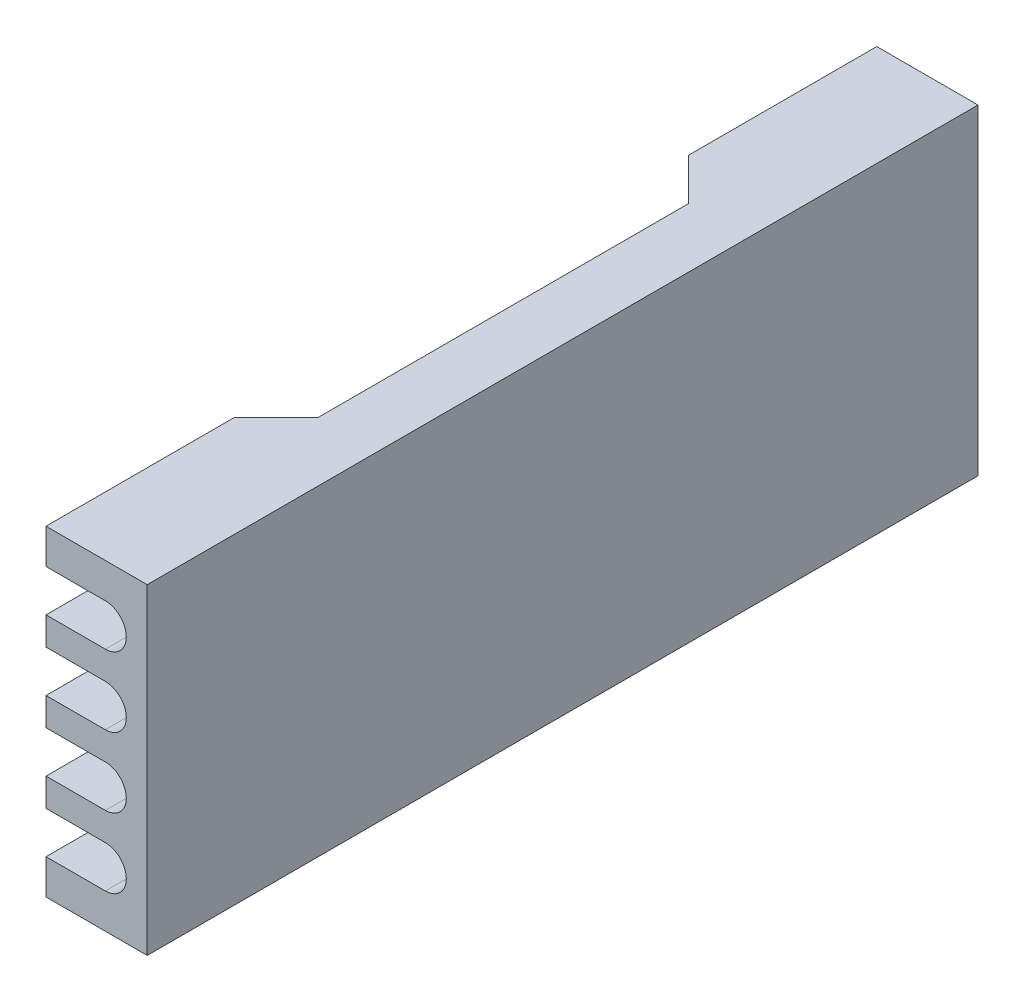
SolidWorks part; units mm, degrees
ref_plane "Front Plane" through (0, 0, 0) normal (0, 0, 1) x (1, 0, 0)
ref_plane "Top Plane" through (0, 0, 0) normal (0, 1, 0) x (1, 0, 0)
ref_plane "Right Plane" through (0, 0, 0) normal (1, 0, 0) x (0, 0, -1)
sketch "Sketch1" plane through (0, 0, 0) normal (1, 0, 0) x (0, 0, -1)
  line L1 (13.335, -5.334) -> (-13.335, -5.334)
  line L2 (13.335, -5.334) -> (13.335, 5.334)
  line L3 (13.335, 5.334) -> (-13.335, 5.334)
  line L4 (-13.335, -5.334) -> (-13.335, 5.334)
  line L5 (13.335, -5.334) -> (-13.335, 5.334) construction
  line L6 (13.335, 5.334) -> (-13.335, -5.334) construction
  line L11 (13.081, -5.08) -> (-13.081, -5.08) construction
  line L12 (13.081, -5.08) -> (13.081, 5.08) construction
  line L13 (13.081, 5.08) -> (-13.081, 5.08) construction
  line L14 (-13.081, -5.08) -> (-13.081, 5.08) construction
  line L15 (13.081, -5.08) -> (-13.081, 5.08) construction
  line L16 (13.081, 5.08) -> (-13.081, -5.08) construction
  point P0 (0, 0)
  point P11 (0, 0)
  dimension "D1" = 26.67
  dimension "D2" = 10.668
  dimension "D4" = 10.16
  dimension "D5" = 26.162
extrude "Boss-Extrude1" add sketch "Sketch1" along normal blind 0.254
extrude "Extrude-Thin1" add sketch "Sketch1<3>" against normal blind 2.921 and the other way up to surface (0.254 mm away) thin other way up to face at (0.254, 0, 0) thin type one direction wall 0.508
sketch "Sketch1<3>" plane through (0, 0, 0) normal (1, 0, 0) x (0, 0, -1) same geometry as "Sketch1"
sketch "Sketch2" plane through (-2.921, 0, 0) normal (-1, 0, 0) x (0, 0, 1)
  line L4 (-13.335, -5.334) -> (13.335, -5.334)
  line L5 (13.335, -5.334) -> (13.335, 5.334)
  line L6 (13.335, 5.334) -> (-13.335, 5.334)
  line L7 (-13.335, 5.334) -> (-13.335, -5.334)
  line L8 (-13.335, -5.334) -> (13.335, -5.334)
  line L9 (13.335, -5.334) -> (13.335, 5.334)
  line L10 (13.335, 5.334) -> (-13.335, 5.334)
  line L11 (-13.335, 5.334) -> (-13.335, -5.334)
  dimension "D1" = 0
ref_plane "Plane1" through (0, 0, 0) normal (0, -1, 0) x (-1, 0, 0)
sketch "Sketch3" plane through (0, 0, 0) normal (0, -1, 0) x (-1, 0, 0)
  line L0 (2.921, -13.335) -> (3.141, -12.954)
  line L1 (3.141, -12.954) -> (3.429, -13.242)
  line L2 (3.429, -13.242) -> (3.429, -13.843)
  line L3 (3.429, -13.843) -> (2.921, -13.843)
  line L4 (2.921, -13.843) -> (2.921, -13.335)
  line L5 (-0.254, -13.843) -> (2.921, -13.843) construction
  line L6 (2.921, 13.335) -> (2.921, -13.335) construction
  dimension "D1" = 0.508
  dimension "D2" = 30
  dimension "D3" = 45
  dimension "D4" = 0.381
sweep "Sweep1" add profiles "Sketch3" path "Sketch2"
sketch "Sketch5" plane through (-3.429, 0, 0) normal (-1, 0, 0) x (0, 0, 1)
  line L0 (13.843, -5.842) -> (-13.843, -5.842) construction
  line L1 (-13.843, 5.842) -> (-15.113, 5.842)
  line L2 (-13.843, 5.842) -> (-13.843, -5.842)
  line L3 (-13.843, -5.842) -> (-15.113, -5.842)
  line L4 (-15.113, 5.842) -> (-15.113, -5.842)
  line L5 (13.843, 5.842) -> (15.113, 5.842)
  line L6 (13.843, 5.842) -> (13.843, -5.842)
  line L7 (13.843, -5.842) -> (15.113, -5.842)
  line L8 (15.113, 5.842) -> (15.113, -5.842)
  dimension "D1" = 1.27
extrude "Boss-Extrude2" add sketch "Sketch5" against normal up to surface (3.683 mm away) up to face at (0.254, 0, 0)
sketch "Sketch4" plane through (0, 0, 15.113) normal (0, 0, 1) x (1, 0, 0)
  line L0 (0, 5.334) -> (0, -5.334) construction
  line L1 (0, -5.08) -> (-2.54, -5.08) construction
  line L2 (0, -5.08) -> (0, 5.08) construction
  line L3 (0, 5.08) -> (-2.54, 5.08) construction
  line L4 (-2.54, -5.08) -> (-2.54, 5.08) construction
  line L5 (0, -5.08) -> (-2.54, 5.08) construction
  line L6 (0, 5.08) -> (-2.54, -5.08) construction
  line L7 (-1.27, 3.81) -> (-1.27, -3.81) construction
  line L8 (-1.27, 4.572) -> (-3.429, 4.572)
  line L10 (-3.429, 4.572) -> (-3.429, 3.048)
  line L11 (-3.429, 3.048) -> (-1.27, 3.048)
  line L12 (-1.27, 3.81) -> (-2.8832, 3.81) construction
  line L13 (-3.429, 5.241) -> (-3.429, 5.842) construction
  arc A0 (-1.27, 3.048) -> (-1.27, 4.572) centre (-1.27, 3.81) ccw
  arc A1 (-1.27, 4.572) -> (-2.032, 3.81) centre (-1.27, 3.81) ccw construction
  arc A2 (-2.032, 3.81) -> (-1.27, 3.048) centre (-1.27, 3.81) ccw construction
  point P2 (-1.27, 0)
  point P7 (-1.27, 0)
  dimension "D4" = 1.524
  dimension "D1" = 10.16
  dimension "D2" = 2.54
  dimension "D3" = 7.62
extrude "Cut-Extrude1" cut sketch "Sketch4" against normal through all and the other way through all
pattern_linear "LPattern1" count 4 spacing 2.54 along (0, -1, 0) of "Cut-Extrude1"
sketch "Sketch7" plane through (0, -5.842, 0) normal (0, -1, 0) x (1, 0, 0)
  line L0 (-3.429, 8.255) -> (-1.905, 6.731)
  line L1 (-3.429, 13.843) -> (-3.429, -13.843) construction
  line L2 (-1.905, 6.731) -> (-1.905, -6.731)
  line L3 (-1.905, -6.731) -> (-3.429, -8.255)
  line L4 (-3.429, -8.255) -> (-3.429, 8.255)
  line L5 (0, 0) -> (-1.905, 0) construction
  point P5 (-1.905, 0)
  dimension "D1" = 16.51
  dimension "D2" = 1.524
  dimension "D3" = 45
extrude "Cut-Extrude2" cut sketch "Sketch7" against normal through all
